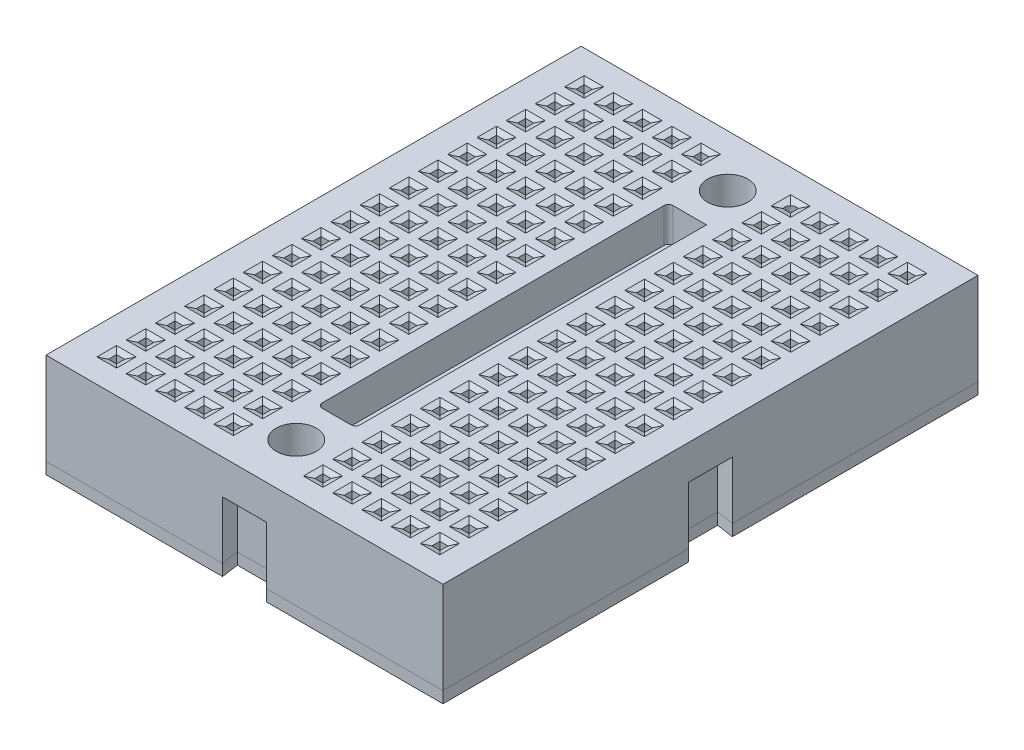
SolidWorks part; units mm, degrees
note: '?' marks a value the reader was unsure of.
ref_plane "Front Plane" through (0, 0, 0) normal (0, 0, 1) x (1, 0, 0)
ref_plane "Top Plane" through (0, 0, 0) normal (0, 1, 0) x (1, 0, 0)
ref_plane "Right Plane" through (0, 0, 0) normal (1, 0, 0) x (0, 0, -1)
sketch "Sketch1" plane through (0, 0, 0) normal (0, 1, 0) x (1, 0, 0)
  line L1 (17.25, -23.25) -> (-17.25, -23.25)
  line L2 (17.25, -23.25) -> (17.25, 23.25)
  line L3 (17.25, 23.25) -> (-17.25, 23.25)
  line L4 (-17.25, -23.25) -> (-17.25, 23.25)
  line L5 (17.25, -23.25) -> (-17.25, 23.25) construction
  line L6 (17.25, 23.25) -> (-17.25, -23.25) construction
  point P0 (0, 0)
  dimension "D1" = 46.5
  dimension "D2" = 34.5
extrude "Boss-Bottom" add sketch "Sketch1" along normal blind 1 from offset 4.5 offset against normal yes
sketch "Sketch2" plane through (0, -3.5, 0) normal (0, 1, 0) x (1, 0, 0)
  line L4 (-17.25, 23.25) -> (-17.25, -23.25)
  line L5 (-17.25, -23.25) -> (17.25, -23.25)
  line L6 (17.25, -23.25) -> (17.25, 23.25)
  line L7 (17.25, 23.25) -> (-17.25, 23.25)
  line L8 (-17.25, 23.25) -> (-17.25, -23.25)
  line L9 (-17.25, -23.25) -> (17.25, -23.25)
  line L10 (17.25, -23.25) -> (17.25, 23.25)
  line L11 (17.25, 23.25) -> (-17.25, 23.25)
  dimension "D2" = 46.5
  dimension "D3" = 34.5
  dimension "D1" = 0
extrude "Boss-Top" add sketch "Sketch2" along normal blind 8 separate body
sketch "Sketch3" plane through (0, 4.5, 0) normal (0, 1, 0) x (1, 0, 0)
  line L0 (0, 15.25) -> (0, 18.75) construction
  line L1 (1.65, -15.25) -> (-1.65, -15.25)
  line L2 (1.65, -15.25) -> (1.65, 15.25)
  line L3 (1.65, 15.25) -> (-1.65, 15.25)
  line L4 (-1.65, -15.25) -> (-1.65, 15.25)
  line L5 (1.65, -15.25) -> (-1.65, 15.25) construction
  line L6 (1.65, 15.25) -> (-1.65, -15.25) construction
  line L7 (0, 0) -> (17.25, 0) construction
  line L8 (17.25, -23.25) -> (17.25, 23.25) construction
  circle A0 centre (0, 18.75) radius 1.75
  circle A1 centre (0, -18.75) radius 1.75
  point P0 (0, 0)
  dimension "D4" = 3.5
  dimension "D1" = 30.5
  dimension "D2" = 3.3
  dimension "D3" = 3.5
extrude "Cut-Middle" cut sketch "Sketch3" against normal blind 3
sketch "Sketch5" plane through (0, 1.5, 0) normal (0, 1, 0) x (1, 0, 0)
  line L0 (0, 0) -> (17.25, 0) construction
  line L1 (17.25, -23.25) -> (17.25, 23.25) construction
  circle A0 centre (0, 18.75) radius 1
  circle A1 centre (0, -18.75) radius 1
  dimension "D1" = 2
extrude "Cut-M2 screw" cut sketch "Sketch5" against normal blind 5
sketch "Sketch6" plane through (0, 4.5, 0) normal (0, 1, 0) x (1, 0, 0)
  line L0 (0, 0) -> (0, 18.75) construction
  line L1 (0, 18.75) -> (16.9, 18.75) construction
  line L2 (16.9, 18.75) -> (16.9, -23.25) construction
  line L3 (-17.25, -23.25) -> (17.25, -23.25) construction
  line L4 (16.9, 18.75) -> (16.9, 23.25) construction
  line L5 (17.25, 23.25) -> (-17.25, 23.25) construction
  line L6 (0, 18.75) -> (0, 23.25) construction
  line L7 (0, 23.25) -> (16.9, 23.25) construction
  line L8 (8.45, 23.25) -> (8.45, 23.05) construction
  line L9 (8.45, 23.05) -> (16.9, 23.05) construction
  line L10 (8.45, 23.05) -> (0, 23.05) construction
  line L11 (11.86, 19.97) -> (11.86, 20.67)
  line L12 (14.4, 19.97) -> (13.7, 19.97)
  line L13 (14.4, 19.97) -> (14.4, 20.67)
  line L14 (14.4, 20.67) -> (13.7, 20.67)
  line L15 (13.7, 19.97) -> (13.7, 20.67)
  line L16 (14.4, 19.97) -> (13.7, 20.67) construction
  line L17 (14.4, 20.67) -> (13.7, 19.97) construction
  line L18 (11.86, 19.97) -> (11.16, 19.97)
  line L19 (11.16, 19.97) -> (11.16, 20.67)
  line L20 (11.86, 20.67) -> (11.16, 20.67)
  line L21 (9.32, 19.97) -> (9.32, 20.67)
  line L22 (9.32, 19.97) -> (8.62, 19.97)
  line L23 (8.62, 19.97) -> (8.62, 20.67)
  line L24 (9.32, 20.67) -> (8.62, 20.67)
  line L25 (6.78, 19.97) -> (6.78, 20.67)
  line L26 (6.78, 19.97) -> (6.08, 19.97)
  line L27 (6.08, 19.97) -> (6.08, 20.67)
  line L28 (6.78, 20.67) -> (6.08, 20.67)
  line L29 (4.24, 19.97) -> (4.24, 20.67)
  line L30 (4.24, 19.97) -> (3.54, 19.97)
  line L31 (3.54, 19.97) -> (3.54, 20.67)
  line L32 (4.24, 20.67) -> (3.54, 20.67)
  line L33 (3.89, 20.67) -> (3.89, 20.32) construction
  line L34 (3.89, 20.32) -> (4.24, 20.32) construction
  point P14 (14.05, 20.32)
  point P39 (6.43, 20.32)
  point P41 (3.89, 20.32)
  point P42 (8.97, 20.32)
  point P43 (11.51, 20.32)
  point P44 (14.05, 20.32)
  dimension "D1" = 16.9
  dimension "D2" = 0.2
  dimension "D3" = 0.7
  dimension "D4" = 2.85
  dimension "D5" = 2.73
  dimension "D6" = 5
extrude "Cut-Extrude3" cut sketch "Sketch6" against normal blind 8
sketch "Sketch7" plane through (0, 4.5, 0) normal (0, 1, 0) x (1, 0, 0)
  line L0 (12.36, 19.47) -> (10.66, 19.47)
  line L1 (14.9, 19.47) -> (13.2, 19.47)
  line L2 (14.9, 19.47) -> (14.9, 21.17)
  line L3 (14.9, 21.17) -> (13.2, 21.17)
  line L4 (13.2, 19.47) -> (13.2, 21.17)
  line L5 (14.9, 19.47) -> (13.2, 21.17) construction
  line L6 (14.9, 21.17) -> (13.2, 19.47) construction
  line L7 (12.36, 19.47) -> (12.36, 21.17)
  line L8 (12.36, 21.17) -> (10.66, 21.17)
  line L9 (10.66, 19.47) -> (10.66, 21.17)
  line L10 (12.36, 19.47) -> (10.66, 21.17) construction
  line L11 (12.36, 21.17) -> (10.66, 19.47) construction
  line L12 (9.82, 19.47) -> (8.12, 19.47)
  line L13 (9.82, 19.47) -> (9.82, 21.17)
  line L14 (9.82, 21.17) -> (8.12, 21.17)
  line L15 (8.12, 19.47) -> (8.12, 21.17)
  line L16 (9.82, 19.47) -> (8.12, 21.17) construction
  line L17 (9.82, 21.17) -> (8.12, 19.47) construction
  line L18 (7.28, 19.47) -> (5.58, 19.47)
  line L19 (7.28, 19.47) -> (7.28, 21.17)
  line L20 (7.28, 21.17) -> (5.58, 21.17)
  line L21 (5.58, 19.47) -> (5.58, 21.17)
  line L22 (7.28, 19.47) -> (5.58, 21.17) construction
  line L23 (7.28, 21.17) -> (5.58, 19.47) construction
  line L24 (4.74, 19.47) -> (3.04, 19.47)
  line L25 (4.74, 19.47) -> (4.74, 21.17)
  line L26 (4.74, 21.17) -> (3.04, 21.17)
  line L27 (3.04, 19.47) -> (3.04, 21.17)
  line L28 (4.74, 19.47) -> (3.04, 21.17) construction
  line L29 (4.74, 21.17) -> (3.04, 19.47) construction
  point P0 (14.05, 20.32)
  point P6 (11.51, 20.32)
  point P11 (8.97, 20.32)
  point P16 (6.43, 20.32)
  point P21 (3.89, 20.32)
  dimension "D1" = 1.7
  dimension "D2" = 5
extrude "Cut-Extrude4" cut sketch "Sketch7" against normal blind 2.54 draft 70
pattern_linear "LPattern3" count 17 spacing 2.54 along (0, 0, 1) of "Cut-Extrude3", "Cut-Extrude4"
mirror "Mirror1" about plane through (0, 0, 0) normal (1, 0, 0) of "LPattern3", "Cut-Extrude3", "Cut-Extrude4"
fillet "Fillet1" radius 0.4 4 edges at (1.65, 3, 15.25) (-1.65, 3, 15.25) (3.54, 0.409, -20.67) (-1.65, 3, -15.25)
sketch "Sketch8" plane through (0, 4.5, 0) normal (0, 1, 0) x (1, 0, 0)
  line L0 (0, 23.25) -> (0, 24.75) construction
  line L1 (1.8928, 24.75) -> (-1.8928, 24.75)
  line L2 (-2.0905, 24.5203) -> (-1.9, 23.25)
  line L3 (-1.9, 23.25) -> (1.9, 23.25)
  line L4 (1.9, 23.25) -> (2.0905, 24.5203)
  line L5 (0, 18.75) -> (0, 23.25) construction
  line L6 (17.25, 23.25) -> (-17.25, 23.25) construction
  line L7 (-17.25, 0) -> (-18.75, 0) construction
  line L8 (-18.75, 1.8928) -> (-18.75, -1.8928)
  line L9 (-18.5203, -2.0905) -> (-17.25, -1.9)
  line L10 (-17.25, -1.9) -> (-17.25, 1.9)
  line L11 (-17.25, 1.9) -> (-18.5203, 2.0905)
  line L12 (0, 0) -> (-17.25, 0) construction
  line L13 (-17.25, 23.25) -> (-17.25, -23.25) construction
  arc A0 (2.0905, 24.5203) -> (1.8928, 24.75) centre (1.8928, 24.55) ccw
  arc A1 (-1.8928, 24.75) -> (-2.0905, 24.5203) centre (-1.8928, 24.55) ccw
  arc A2 (-18.5203, 2.0905) -> (-18.75, 1.8928) centre (-18.55, 1.8928) ccw
  arc A3 (-18.75, -1.8928) -> (-18.5203, -2.0905) centre (-18.55, -1.8928) ccw
extrude "Boss-Connector" add sketch "Sketch8" against normal blind 5 from offset 3 separate body offset against normal yes
sketch "Sketch9" plane through (0, 4.5, 0) normal (0, 1, 0) x (1, 0, 0)
  line L0 (17.25, 0) -> (15.75, 0) construction
  line L1 (15.75, 1.8928) -> (15.75, -1.8928)
  line L2 (15.75, -2.125) -> (17.25, -1.9)
  line L3 (17.25, -1.9) -> (17.25, 1.9)
  line L4 (17.25, 1.9) -> (15.75, 2.125)
  line L5 (0, 0) -> (17.25, 0) construction
  line L6 (17.25, -23.25) -> (17.25, 23.25) construction
  line L7 (0, -23.25) -> (0, -21.75) construction
  line L8 (1.8928, -21.75) -> (-1.8928, -21.75)
  line L9 (-2.125, -21.75) -> (-1.9, -23.25)
  line L10 (-1.9, -23.25) -> (1.9, -23.25)
  line L11 (1.9, -23.25) -> (2.125, -21.75)
  line L12 (0, 0) -> (0, -23.25) construction
  line L13 (-17.25, -23.25) -> (17.25, -23.25) construction
  line L14 (1.8928, -21.75) -> (2.125, -21.75)
  line L15 (-1.8928, -21.75) -> (-2.125, -21.75)
  line L16 (15.75, 1.8928) -> (15.75, 2.125)
  line L17 (15.75, -1.8928) -> (15.75, -2.125)
  arc A0 (15.9797, 2.0905) -> (15.75, 1.8928) centre (15.95, 1.8928) ccw construction
  arc A1 (15.75, -1.8928) -> (15.9797, -2.0905) centre (15.95, -1.8928) ccw construction
  arc A2 (2.0905, -21.9797) -> (1.8928, -21.75) centre (1.8928, -21.95) ccw construction
  arc A3 (-1.8928, -21.75) -> (-2.0905, -21.9797) centre (-1.8928, -21.95) ccw construction
  dimension "D2" = 3.7855
  dimension "D3" = 3.8
  dimension "D5" = 23.25
extrude "Cut-Connector" cut sketch "Sketch9" against normal blind 6 from offset 3 offset against normal yes
ref_plane "Plane1" through (0, 2.5, 0) normal (0, 1, 0) x (1, 0, 0)
sketch "Sketch10" plane through (0, 2.5, 0) normal (0, 1, 0) x (1, 0, 0)
  line L0 (14.4, 20.67) -> (14.9, 21.17) construction
  line L2 (14.4, 19.97) -> (14.9, 19.47) construction
  line L3 (11.16, 19.97) -> (10.66, 19.47) construction
  line L4 (11.16, 20.67) -> (10.66, 21.17) construction
  line L5 (8.62, 20.67) -> (8.12, 21.17) construction
  line L6 (8.62, 19.97) -> (8.12, 19.47) construction
  line L7 (6.78, 20.67) -> (7.28, 21.17) construction
  line L8 (6.78, 19.97) -> (7.28, 19.47) construction
  line L9 (4.24, 19.97) -> (4.74, 19.47) construction
  point P0 (14.05, 20.32)
  point P1 (11.51, 20.32)
  point P2 (8.97, 20.32)
  point P3 (6.43, 20.32)
  point P4 (3.8848, 20.3252)
  point P6 (14.0799, 17.7806)
  point P30 (11.5399, 17.7806)
  point P31 (8.9999, 17.7806)
  point P32 (6.4599, 17.7806)
  point P33 (3.9147, 17.7858)
  point P34 (14.1016, 15.2623)
  point P35 (11.5616, 15.2623)
  point P36 (9.0216, 15.2623)
  point P37 (6.4816, 15.2623)
  point P38 (3.9364, 15.2676)
  point P39 (14.0487, 12.7209)
  point P40 (11.5087, 12.7209)
  point P41 (8.9687, 12.7209)
  point P42 (6.4287, 12.7209)
  point P43 (3.8835, 12.7262)
  point P44 (14.0487, 10.1749)
  point P45 (11.5087, 10.1749)
  point P46 (8.9687, 10.1749)
  point P47 (6.4287, 10.1749)
  point P48 (3.8835, 10.1801)
  point P49 (14.0548, 7.6501)
  point P50 (11.5148, 7.6501)
  point P51 (8.9748, 7.6501)
  point P52 (6.4348, 7.6501)
  point P53 (3.8896, 7.6553)
  point P54 (14.1089, 5.0642)
  point P55 (11.5689, 5.0642)
  point P56 (9.0289, 5.0642)
  point P57 (6.4889, 5.0642)
  point P58 (3.9437, 5.0694)
  point P59 (14.031, 2.5387)
  point P60 (11.491, 2.5387)
  point P61 (8.951, 2.5387)
  point P62 (6.411, 2.5387)
  point P63 (3.8658, 2.5439)
  point P64 (14.0455, -0.0484)
  point P65 (11.5055, -0.0484)
  point P66 (8.9655, -0.0484)
  point P67 (6.4255, -0.0484)
  point P68 (3.8803, -0.0432)
  point P69 (14.0174, -2.484)
  point P70 (11.4774, -2.484)
  point P71 (8.9374, -2.484)
  point P72 (6.3974, -2.484)
  point P73 (3.8521, -2.4788)
  point P74 (13.9866, -5.1019)
  point P75 (11.4466, -5.1019)
  point P76 (8.9066, -5.1019)
  point P77 (6.3666, -5.1019)
  point P78 (3.8213, -5.0967)
  point P79 (13.9866, -7.5966)
  point P80 (11.4466, -7.5966)
  point P81 (8.9066, -7.5966)
  point P82 (6.3666, -7.5966)
  point P83 (3.8213, -7.5914)
  point P84 (14.0174, -10.1529)
  point P85 (11.4774, -10.1529)
  point P86 (8.9374, -10.1529)
  point P87 (6.3974, -10.1529)
  point P88 (3.8521, -10.1476)
  point P89 (14.0719, -12.7703)
  point P90 (11.5319, -12.7703)
  point P91 (8.9919, -12.7703)
  point P92 (6.4519, -12.7703)
  point P93 (3.9067, -12.7651)
  point P99 (8.9893, -0.0026)
  point P100 (6.4493, -0.0026)
  point P101 (3.9093, -0.0026)
  point P103 (-3.9057, -7.6019)
  point P104 (14.0201, -17.8449)
  point P105 (11.4801, -17.8449)
  point P106 (8.9401, -17.8449)
  point P107 (6.4001, -17.8449)
  point P108 (3.8549, -17.8397)
  point P110 (14.0693, -15.2705)
  point P111 (11.5293, -15.2705)
  point P112 (8.9893, -15.2705)
  point P113 (6.4493, -15.2705)
  point P114 (3.9041, -15.2653)
  point P115 (14.0249, -20.3204)
  point P116 (11.4849, -20.3204)
  point P117 (8.9449, -20.3204)
  point P118 (6.4049, -20.3204)
  point P119 (3.8597, -20.3152)
  point P120 (-3.9022, -20.3215)
  point P121 (-6.4422, -20.3215)
  point P122 (-8.9822, -20.3215)
  point P123 (-11.5222, -20.3215)
  point P124 (-14.0674, -20.3163)
  point P130 (-3.9591, -17.7916)
  point P131 (-6.4991, -17.7916)
  point P132 (-9.0391, -17.7916)
  point P133 (-11.5791, -17.7916)
  point P134 (-14.1243, -17.7864)
  point P135 (-3.9306, -15.2901)
  point P136 (-6.4706, -15.2901)
  point P137 (-9.0106, -15.2901)
  point P138 (-11.5506, -15.2901)
  point P139 (-14.0959, -15.2849)
  point P140 (-3.9591, -12.7886)
  point P141 (-6.4991, -12.7886)
  point P142 (-9.0391, -12.7886)
  point P143 (-11.5791, -12.7886)
  point P144 (-14.1243, -12.7834)
  point P145 (-3.9306, -10.2303)
  point P146 (-6.4706, -10.2303)
  point P147 (-9.0106, -10.2303)
  point P148 (-11.5506, -10.2303)
  point P149 (-14.0959, -10.2251)
  point P154 (-6.4457, -7.6019)
  point P155 (-8.9857, -7.6019)
  point P156 (-11.5257, -7.6019)
  point P157 (-14.0709, -7.5967)
  point P158 (-3.9291, -5.0801)
  point P159 (-6.4691, -5.0801)
  point P160 (-9.0091, -5.0801)
  point P161 (-11.5491, -5.0801)
  point P162 (-14.0943, -5.0749)
  point P163 (-3.8809, -2.5371)
  point P164 (-6.4209, -2.5371)
  point P165 (-8.9609, -2.5371)
  point P166 (-11.5009, -2.5371)
  point P167 (-14.0462, -2.5319)
  point P168 (-3.8994, -0.0477)
  point P169 (-6.4394, -0.0477)
  point P170 (-8.9794, -0.0477)
  point P171 (-11.5194, -0.0477)
  point P172 (-14.0646, -0.0425)
  point P173 (-3.8809, 2.497)
  point P174 (-6.4209, 2.497)
  point P175 (-8.9609, 2.497)
  point P176 (-11.5009, 2.497)
  point P177 (-14.0462, 2.5022)
  point P178 (-3.8749, 5.0444)
  point P179 (-6.4149, 5.0444)
  point P180 (-8.9549, 5.0444)
  point P181 (-11.4949, 5.0444)
  point P182 (-14.0401, 5.0496)
  point P183 (-3.9063, 7.6157)
  point P184 (-6.4463, 7.6157)
  point P185 (-8.9863, 7.6157)
  point P186 (-11.5263, 7.6157)
  point P187 (-14.0715, 7.6209)
  point P188 (-3.935, 10.1531)
  point P189 (-6.475, 10.1531)
  point P190 (-9.015, 10.1531)
  point P191 (-11.555, 10.1531)
  point P192 (-14.1002, 10.1583)
  point P193 (-3.935, 12.5989)
  point P194 (-6.475, 12.5989)
  point P195 (-9.015, 12.5989)
  point P196 (-11.555, 12.5989)
  point P197 (-14.1002, 12.6042)
  point P198 (-3.8723, 15.1703)
  point P199 (-6.4123, 15.1703)
  point P200 (-8.9523, 15.1703)
  point P201 (-11.4923, 15.1703)
  point P202 (-14.0375, 15.1755)
  point P203 (-3.935, 17.7102)
  point P204 (-6.475, 17.7102)
  point P205 (-9.015, 17.7102)
  point P206 (-11.555, 17.7102)
  point P207 (-14.1002, 17.7154)
  point P208 (-3.8914, 20.2984)
  point P209 (-6.4314, 20.2984)
  point P210 (-8.9714, 20.2984)
  point P211 (-11.5114, 20.2984)
  point P212 (-14.0566, 20.3036)
fillet "Fillet2" [suppressed] radius 0.4
fillet "Fillet3" [suppressed] radius 0.4
other "CPoint1" parameters "Diameter"=2, "StubLength"=2
ref_axis "Axis1" through (14.05, 12.5, -20.32) along (0, -1, 0)?
other "CPoint2" parameters "Diameter"=2, "StubLength"=2
ref_axis "Axis2" through (11.51, 12.5, -20.32) along (0, -1, 0)?
other "CPoint3" parameters "Diameter"=2, "StubLength"=2
ref_axis "Axis3" through (8.97, 12.5, -20.32) along (0, -1, 0)?
other "CPoint4" parameters "Diameter"=2, "StubLength"=2
ref_axis "Axis4" through (6.43, 12.5, -20.32) along (0, -1, 0)?
other "CPoint5" parameters "Diameter"=2, "StubLength"=2
ref_axis "Axis5" through (3.8848, 12.5, -20.3252) along (0, -1, 0)?
other "CPoint6" parameters "Diameter"=2, "StubLength"=2
ref_axis "Axis6" through (14.0799, 12.5, -17.7806) along (0, -1, 0)?
other "CPoint7" parameters "Diameter"=2, "StubLength"=2
ref_axis "Axis7" through (11.5399, 12.5, -17.7806) along (0, -1, 0)?
other "CPoint8" parameters "Diameter"=2, "StubLength"=2
ref_axis "Axis8" through (8.9999, 12.5, -17.7806) along (0, -1, 0)?
other "CPoint9" parameters "Diameter"=2, "StubLength"=2
ref_axis "Axis9" through (6.4599, 12.5, -17.7806) along (0, -1, 0)?
other "CPoint10" parameters "Diameter"=2, "StubLength"=2
ref_axis "Axis10" through (3.9147, 12.5, -17.7858) along (0, -1, 0)?
other "CPoint11" parameters "Diameter"=2, "StubLength"=2
ref_axis "Axis11" through (14.1016, 12.5, -15.2623) along (0, -1, 0)?
other "CPoint12" parameters "Diameter"=2, "StubLength"=2
ref_axis "Axis12" through (11.5616, 12.5, -15.2623) along (0, -1, 0)?
other "CPoint13" parameters "Diameter"=2, "StubLength"=2
ref_axis "Axis13" through (9.0216, 12.5, -15.2623) along (0, -1, 0)?
other "CPoint14" parameters "Diameter"=2, "StubLength"=2
ref_axis "Axis14" through (6.4816, 12.5, -15.2623) along (0, -1, 0)?
other "CPoint15" parameters "Diameter"=2, "StubLength"=2
ref_axis "Axis15" through (3.9364, 12.5, -15.2676) along (0, -1, 0)?
other "CPoint16" parameters "Diameter"=2, "StubLength"=2
ref_axis "Axis16" through (14.0487, 12.5, -12.7209) along (0, -1, 0)?
other "CPoint17" parameters "Diameter"=2, "StubLength"=2
ref_axis "Axis17" through (11.5087, 12.5, -12.7209) along (0, -1, 0)?
other "CPoint18" parameters "Diameter"=2, "StubLength"=2
ref_axis "Axis18" through (8.9687, 12.5, -12.7209) along (0, -1, 0)?
other "CPoint19" parameters "Diameter"=2, "StubLength"=2
ref_axis "Axis19" through (6.4287, 12.5, -12.7209) along (0, -1, 0)?
other "CPoint20" parameters "Diameter"=2, "StubLength"=2
ref_axis "Axis20" through (3.8835, 12.5, -12.7262) along (0, -1, 0)?
other "CPoint21" parameters "Diameter"=2, "StubLength"=2
ref_axis "Axis21" through (14.0487, 12.5, -10.1749) along (0, -1, 0)?
other "CPoint22" parameters "Diameter"=2, "StubLength"=2
ref_axis "Axis22" through (11.5087, 12.5, -10.1749) along (0, -1, 0)?
other "CPoint23" parameters "Diameter"=2, "StubLength"=2
ref_axis "Axis23" through (8.9687, 12.5, -10.1749) along (0, -1, 0)?
other "CPoint24" parameters "Diameter"=2, "StubLength"=2
ref_axis "Axis24" through (6.4287, 12.5, -10.1749) along (0, -1, 0)?
other "CPoint25" parameters "Diameter"=2, "StubLength"=2
ref_axis "Axis25" through (3.8835, 12.5, -10.1801) along (0, -1, 0)?
other "CPoint26" parameters "Diameter"=2, "StubLength"=2
ref_axis "Axis26" through (14.0548, 12.5, -7.6501) along (0, -1, 0)?
other "CPoint27" parameters "Diameter"=2, "StubLength"=2
ref_axis "Axis27" through (11.5148, 12.5, -7.6501) along (0, -1, 0)?
other "CPoint28" parameters "Diameter"=2, "StubLength"=2
ref_axis "Axis28" through (8.9748, 12.5, -7.6501) along (0, -1, 0)?
other "CPoint29" parameters "Diameter"=2, "StubLength"=2
ref_axis "Axis29" through (6.4348, 12.5, -7.6501) along (0, -1, 0)?
other "CPoint30" parameters "Diameter"=2, "StubLength"=2
ref_axis "Axis30" through (3.8896, 12.5, -7.6553) along (0, -1, 0)?
other "CPoint31" parameters "Diameter"=2, "StubLength"=2
ref_axis "Axis31" through (14.1089, 12.5, -5.0642) along (0, -1, 0)?
other "CPoint32" parameters "Diameter"=2, "StubLength"=2
ref_axis "Axis32" through (11.5689, 12.5, -5.0642) along (0, -1, 0)?
other "CPoint33" parameters "Diameter"=2, "StubLength"=2
ref_axis "Axis33" through (9.0289, 12.5, -5.0642) along (0, -1, 0)?
other "CPoint34" parameters "Diameter"=2, "StubLength"=2
ref_axis "Axis34" through (6.4889, 12.5, -5.0642) along (0, -1, 0)?
other "CPoint35" parameters "Diameter"=2, "StubLength"=2
ref_axis "Axis35" through (3.9437, 12.5, -5.0694) along (0, -1, 0)?
other "CPoint36" parameters "Diameter"=2, "StubLength"=2
ref_axis "Axis36" through (14.031, 12.5, -2.5387) along (0, -1, 0)?
other "CPoint37" parameters "Diameter"=2, "StubLength"=2
ref_axis "Axis37" through (11.491, 12.5, -2.5387) along (0, -1, 0)?
other "CPoint38" parameters "Diameter"=2, "StubLength"=2
ref_axis "Axis38" through (8.951, 12.5, -2.5387) along (0, -1, 0)?
other "CPoint39" parameters "Diameter"=2, "StubLength"=2
ref_axis "Axis39" through (6.411, 12.5, -2.5387) along (0, -1, 0)?
other "CPoint40" parameters "Diameter"=2, "StubLength"=2
ref_axis "Axis40" through (3.8658, 12.5, -2.5439) along (0, -1, 0)?
other "CPoint41" parameters "Diameter"=2, "StubLength"=2
ref_axis "Axis41" through (14.0455, 12.5, 0.0484) along (0, -1, 0)?
other "CPoint42" parameters "Diameter"=2, "StubLength"=2
ref_axis "Axis42" through (11.5055, 12.5, 0.0484) along (0, -1, 0)?
other "CPoint43" parameters "Diameter"=2, "StubLength"=2
ref_axis "Axis43" through (8.9655, 12.5, 0.0484) along (0, -1, 0)?
other "CPoint44" parameters "Diameter"=2, "StubLength"=2
ref_axis "Axis44" through (6.4255, 12.5, 0.0484) along (0, -1, 0)?
other "CPoint45" parameters "Diameter"=2, "StubLength"=2
ref_axis "Axis45" through (3.8803, 12.5, 0.0432) along (0, -1, 0)?
other "CPoint46" parameters "Diameter"=2, "StubLength"=2
ref_axis "Axis46" through (14.0174, 12.5, 2.484) along (0, -1, 0)?
other "CPoint47" parameters "Diameter"=2, "StubLength"=2
ref_axis "Axis47" through (11.4774, 12.5, 2.484) along (0, -1, 0)?
other "CPoint48" parameters "Diameter"=2, "StubLength"=2
ref_axis "Axis48" through (8.9374, 12.5, 2.484) along (0, -1, 0)?
other "CPoint49" parameters "Diameter"=2, "StubLength"=2
ref_axis "Axis49" through (6.3974, 12.5, 2.484) along (0, -1, 0)?
other "CPoint50" parameters "Diameter"=2, "StubLength"=2
ref_axis "Axis50" through (3.8521, 12.5, 2.4788) along (0, -1, 0)?
other "CPoint51" parameters "Diameter"=2, "StubLength"=2
ref_axis "Axis51" through (13.9866, 12.5, 5.1019) along (0, -1, 0)?
other "CPoint52" parameters "Diameter"=2, "StubLength"=2
ref_axis "Axis52" through (11.4466, 12.5, 5.1019) along (0, -1, 0)?
other "CPoint53" parameters "Diameter"=2, "StubLength"=2
ref_axis "Axis53" through (8.9066, 12.5, 5.1019) along (0, -1, 0)?
other "CPoint54" parameters "Diameter"=2, "StubLength"=2
ref_axis "Axis54" through (6.3666, 12.5, 5.1019) along (0, -1, 0)?
other "CPoint55" parameters "Diameter"=2, "StubLength"=2
ref_axis "Axis55" through (3.8213, 12.5, 5.0967) along (0, -1, 0)?
other "CPoint56" parameters "Diameter"=2, "StubLength"=2
ref_axis "Axis56" through (13.9866, 12.5, 7.5966) along (0, -1, 0)?
other "CPoint57" parameters "Diameter"=2, "StubLength"=2
ref_axis "Axis57" through (11.4466, 12.5, 7.5966) along (0, -1, 0)?
other "CPoint58" parameters "Diameter"=2, "StubLength"=2
ref_axis "Axis58" through (8.9066, 12.5, 7.5966) along (0, -1, 0)?
other "CPoint59" parameters "Diameter"=2, "StubLength"=2
ref_axis "Axis59" through (6.3666, 12.5, 7.5966) along (0, -1, 0)?
other "CPoint60" parameters "Diameter"=2, "StubLength"=2
ref_axis "Axis60" through (3.8213, 12.5, 7.5914) along (0, -1, 0)?
other "CPoint61" parameters "Diameter"=2, "StubLength"=2
ref_axis "Axis61" through (14.0174, 12.5, 10.1529) along (0, -1, 0)?
other "CPoint62" parameters "Diameter"=2, "StubLength"=2
ref_axis "Axis62" through (11.4774, 12.5, 10.1529) along (0, -1, 0)?
other "CPoint63" parameters "Diameter"=2, "StubLength"=2
ref_axis "Axis63" through (8.9374, 12.5, 10.1529) along (0, -1, 0)?
other "CPoint64" parameters "Diameter"=2, "StubLength"=2
ref_axis "Axis64" through (6.3974, 12.5, 10.1529) along (0, -1, 0)?
other "CPoint65" parameters "Diameter"=2, "StubLength"=2
ref_axis "Axis65" through (3.8521, 12.5, 10.1476) along (0, -1, 0)?
other "CPoint66" parameters "Diameter"=2, "StubLength"=2
ref_axis "Axis66" through (14.0719, 12.5, 12.7703) along (0, -1, 0)?
other "CPoint67" parameters "Diameter"=2, "StubLength"=2
ref_axis "Axis67" through (11.5319, 12.5, 12.7703) along (0, -1, 0)?
other "CPoint68" parameters "Diameter"=2, "StubLength"=2
ref_axis "Axis68" through (8.9919, 12.5, 12.7703) along (0, -1, 0)?
other "CPoint69" parameters "Diameter"=2, "StubLength"=2
ref_axis "Axis69" through (6.4519, 12.5, 12.7703) along (0, -1, 0)?
other "CPoint70" parameters "Diameter"=2, "StubLength"=2
ref_axis "Axis70" through (3.9067, 12.5, 12.7651) along (0, -1, 0)?
other "CPoint71" parameters "Diameter"=2, "StubLength"=2
ref_axis "Axis71" through (8.9893, 12.5, 0.0026) along (0, -1, 0)?
other "CPoint72" parameters "Diameter"=2, "StubLength"=2
ref_axis "Axis72" through (6.4493, 12.5, 0.0026) along (0, -1, 0)?
other "CPoint73" parameters "Diameter"=2, "StubLength"=2
ref_axis "Axis73" through (3.9093, 12.5, 0.0026) along (0, -1, 0)?
other "CPoint74" parameters "Diameter"=2, "StubLength"=2
ref_axis "Axis74" through (-3.9057, 12.5, 7.6019) along (0, -1, 0)?
other "CPoint75" parameters "Diameter"=2, "StubLength"=2
ref_axis "Axis75" through (14.0201, 12.5, 17.8449) along (0, -1, 0)?
other "CPoint76" parameters "Diameter"=2, "StubLength"=2
ref_axis "Axis76" through (11.4801, 12.5, 17.8449) along (0, -1, 0)?
other "CPoint77" parameters "Diameter"=2, "StubLength"=2
ref_axis "Axis77" through (8.9401, 12.5, 17.8449) along (0, -1, 0)?
other "CPoint78" parameters "Diameter"=2, "StubLength"=2
ref_axis "Axis78" through (6.4001, 12.5, 17.8449) along (0, -1, 0)?
other "CPoint79" parameters "Diameter"=2, "StubLength"=2
ref_axis "Axis79" through (3.8549, 12.5, 17.8397) along (0, -1, 0)?
other "CPoint80" parameters "Diameter"=2, "StubLength"=2
ref_axis "Axis80" through (14.0693, 12.5, 15.2705) along (0, -1, 0)?
other "CPoint81" parameters "Diameter"=2, "StubLength"=2
ref_axis "Axis81" through (11.5293, 12.5, 15.2705) along (0, -1, 0)?
other "CPoint82" parameters "Diameter"=2, "StubLength"=2
ref_axis "Axis82" through (8.9893, 12.5, 15.2705) along (0, -1, 0)?
other "CPoint83" parameters "Diameter"=2, "StubLength"=2
ref_axis "Axis83" through (6.4493, 12.5, 15.2705) along (0, -1, 0)?
other "CPoint84" parameters "Diameter"=2, "StubLength"=2
ref_axis "Axis84" through (3.9041, 12.5, 15.2653) along (0, -1, 0)?
other "CPoint85" parameters "Diameter"=2, "StubLength"=2
ref_axis "Axis85" through (14.0249, 12.5, 20.3204) along (0, -1, 0)?
other "CPoint86" parameters "Diameter"=2, "StubLength"=2
ref_axis "Axis86" through (11.4849, 12.5, 20.3204) along (0, -1, 0)?
other "CPoint87" parameters "Diameter"=2, "StubLength"=2
ref_axis "Axis87" through (8.9449, 12.5, 20.3204) along (0, -1, 0)?
other "CPoint88" parameters "Diameter"=2, "StubLength"=2
ref_axis "Axis88" through (6.4049, 12.5, 20.3204) along (0, -1, 0)?
other "CPoint89" parameters "Diameter"=2, "StubLength"=2
ref_axis "Axis89" through (3.8597, 12.5, 20.3152) along (0, -1, 0)?
other "CPoint90" parameters "Diameter"=2, "StubLength"=2
ref_axis "Axis90" through (-3.9022, 12.5, 20.3215) along (0, -1, 0)?
other "CPoint91" parameters "Diameter"=2, "StubLength"=2
ref_axis "Axis91" through (-6.4422, 12.5, 20.3215) along (0, -1, 0)?
other "CPoint92" parameters "Diameter"=2, "StubLength"=2
ref_axis "Axis92" through (-8.9822, 12.5, 20.3215) along (0, -1, 0)?
other "CPoint93" parameters "Diameter"=2, "StubLength"=2
ref_axis "Axis93" through (-11.5222, 12.5, 20.3215) along (0, -1, 0)?
other "CPoint94" parameters "Diameter"=2, "StubLength"=2
ref_axis "Axis94" through (-14.0674, 12.5, 20.3163) along (0, -1, 0)?
other "CPoint95" parameters "Diameter"=2, "StubLength"=2
ref_axis "Axis95" through (-3.9591, 12.5, 17.7916) along (0, -1, 0)?
other "CPoint96" parameters "Diameter"=2, "StubLength"=2
ref_axis "Axis96" through (-6.4991, 12.5, 17.7916) along (0, -1, 0)?
other "CPoint97" parameters "Diameter"=2, "StubLength"=2
ref_axis "Axis97" through (-9.0391, 12.5, 17.7916) along (0, -1, 0)?
other "CPoint98" parameters "Diameter"=2, "StubLength"=2
ref_axis "Axis98" through (-11.5791, 12.5, 17.7916) along (0, -1, 0)?
other "CPoint99" parameters "Diameter"=2, "StubLength"=2
ref_axis "Axis99" through (-14.1243, 12.5, 17.7864) along (0, -1, 0)?
other "CPoint100" parameters "Diameter"=2, "StubLength"=2
ref_axis "Axis100" through (-3.9306, 12.5, 15.2901) along (0, -1, 0)?
other "CPoint101" parameters "Diameter"=2, "StubLength"=2
ref_axis "Axis101" through (-6.4706, 12.5, 15.2901) along (0, -1, 0)?
other "CPoint102" parameters "Diameter"=2, "StubLength"=2
ref_axis "Axis102" through (-9.0106, 12.5, 15.2901) along (0, -1, 0)?
other "CPoint103" parameters "Diameter"=2, "StubLength"=2
ref_axis "Axis103" through (-11.5506, 12.5, 15.2901) along (0, -1, 0)?
other "CPoint104" parameters "Diameter"=2, "StubLength"=2
ref_axis "Axis104" through (-14.0959, 12.5, 15.2849) along (0, -1, 0)?
other "CPoint105" parameters "Diameter"=2, "StubLength"=2
ref_axis "Axis105" through (-3.9591, 12.5, 12.7886) along (0, -1, 0)?
other "CPoint106" parameters "Diameter"=2, "StubLength"=2
ref_axis "Axis106" through (-6.4991, 12.5, 12.7886) along (0, -1, 0)?
other "CPoint107" parameters "Diameter"=2, "StubLength"=2
ref_axis "Axis107" through (-9.0391, 12.5, 12.7886) along (0, -1, 0)?
other "CPoint108" parameters "Diameter"=2, "StubLength"=2
ref_axis "Axis108" through (-11.5791, 12.5, 12.7886) along (0, -1, 0)?
other "CPoint109" parameters "Diameter"=2, "StubLength"=2
ref_axis "Axis109" through (-14.1243, 12.5, 12.7834) along (0, -1, 0)?
other "CPoint110" parameters "Diameter"=2, "StubLength"=2
ref_axis "Axis110" through (-3.9306, 12.5, 10.2303) along (0, -1, 0)?
other "CPoint111" parameters "Diameter"=2, "StubLength"=2
ref_axis "Axis111" through (-6.4706, 12.5, 10.2303) along (0, -1, 0)?
other "CPoint112" parameters "Diameter"=2, "StubLength"=2
ref_axis "Axis112" through (-9.0106, 12.5, 10.2303) along (0, -1, 0)?
other "CPoint113" parameters "Diameter"=2, "StubLength"=2
ref_axis "Axis113" through (-11.5506, 12.5, 10.2303) along (0, -1, 0)?
other "CPoint114" parameters "Diameter"=2, "StubLength"=2
ref_axis "Axis114" through (-14.0959, 12.5, 10.2251) along (0, -1, 0)?
other "CPoint115" parameters "Diameter"=2, "StubLength"=2
ref_axis "Axis115" through (-6.4457, 12.5, 7.6019) along (0, -1, 0)?
other "CPoint116" parameters "Diameter"=2, "StubLength"=2
ref_axis "Axis116" through (-8.9857, 12.5, 7.6019) along (0, -1, 0)?
other "CPoint117" parameters "Diameter"=2, "StubLength"=2
ref_axis "Axis117" through (-11.5257, 12.5, 7.6019) along (0, -1, 0)?
other "CPoint118" parameters "Diameter"=2, "StubLength"=2
ref_axis "Axis118" through (-14.0709, 12.5, 7.5967) along (0, -1, 0)?
other "CPoint119" parameters "Diameter"=2, "StubLength"=2
ref_axis "Axis119" through (-3.9291, 12.5, 5.0801) along (0, -1, 0)?
other "CPoint120" parameters "Diameter"=2, "StubLength"=2
ref_axis "Axis120" through (-6.4691, 12.5, 5.0801) along (0, -1, 0)?
other "CPoint121" parameters "Diameter"=2, "StubLength"=2
ref_axis "Axis121" through (-9.0091, 12.5, 5.0801) along (0, -1, 0)?
other "CPoint122" parameters "Diameter"=2, "StubLength"=2
ref_axis "Axis122" through (-11.5491, 12.5, 5.0801) along (0, -1, 0)?
other "CPoint123" parameters "Diameter"=2, "StubLength"=2
ref_axis "Axis123" through (-14.0943, 12.5, 5.0749) along (0, -1, 0)?
other "CPoint124" parameters "Diameter"=2, "StubLength"=2
ref_axis "Axis124" through (-3.8809, 12.5, 2.5371) along (0, -1, 0)?
other "CPoint125" parameters "Diameter"=2, "StubLength"=2
ref_axis "Axis125" through (-6.4209, 12.5, 2.5371) along (0, -1, 0)?
other "CPoint126" parameters "Diameter"=2, "StubLength"=2
ref_axis "Axis126" through (-8.9609, 12.5, 2.5371) along (0, -1, 0)?
other "CPoint127" parameters "Diameter"=2, "StubLength"=2
ref_axis "Axis127" through (-11.5009, 12.5, 2.5371) along (0, -1, 0)?
other "CPoint128" parameters "Diameter"=2, "StubLength"=2
ref_axis "Axis128" through (-14.0462, 12.5, 2.5319) along (0, -1, 0)?
other "CPoint129" parameters "Diameter"=2, "StubLength"=2
ref_axis "Axis129" through (-3.8994, 12.5, 0.0477) along (0, -1, 0)?
other "CPoint130" parameters "Diameter"=2, "StubLength"=2
ref_axis "Axis130" through (-6.4394, 12.5, 0.0477) along (0, -1, 0)?
other "CPoint131" parameters "Diameter"=2, "StubLength"=2
ref_axis "Axis131" through (-8.9794, 12.5, 0.0477) along (0, -1, 0)?
other "CPoint132" parameters "Diameter"=2, "StubLength"=2
ref_axis "Axis132" through (-11.5194, 12.5, 0.0477) along (0, -1, 0)?
other "CPoint133" parameters "Diameter"=2, "StubLength"=2
ref_axis "Axis133" through (-14.0646, 12.5, 0.0425) along (0, -1, 0)?
other "CPoint134" parameters "Diameter"=2, "StubLength"=2
ref_axis "Axis134" through (-3.8809, 12.5, -2.497) along (0, -1, 0)?
other "CPoint135" parameters "Diameter"=2, "StubLength"=2
ref_axis "Axis135" through (-6.4209, 12.5, -2.497) along (0, -1, 0)?
other "CPoint136" parameters "Diameter"=2, "StubLength"=2
ref_axis "Axis136" through (-8.9609, 12.5, -2.497) along (0, -1, 0)?
other "CPoint137" parameters "Diameter"=2, "StubLength"=2
ref_axis "Axis137" through (-11.5009, 12.5, -2.497) along (0, -1, 0)?
other "CPoint138" parameters "Diameter"=2, "StubLength"=2
ref_axis "Axis138" through (-14.0462, 12.5, -2.5022) along (0, -1, 0)?
other "CPoint139" parameters "Diameter"=2, "StubLength"=2
ref_axis "Axis139" through (-3.8749, 12.5, -5.0444) along (0, -1, 0)?
other "CPoint140" parameters "Diameter"=2, "StubLength"=2
ref_axis "Axis140" through (-6.4149, 12.5, -5.0444) along (0, -1, 0)?
other "CPoint141" parameters "Diameter"=2, "StubLength"=2
ref_axis "Axis141" through (-8.9549, 12.5, -5.0444) along (0, -1, 0)?
other "CPoint142" parameters "Diameter"=2, "StubLength"=2
ref_axis "Axis142" through (-11.4949, 12.5, -5.0444) along (0, -1, 0)?
other "CPoint143" parameters "Diameter"=2, "StubLength"=2
ref_axis "Axis143" through (-14.0401, 12.5, -5.0496) along (0, -1, 0)?
other "CPoint144" parameters "Diameter"=2, "StubLength"=2
ref_axis "Axis144" through (-3.9063, 12.5, -7.6157) along (0, -1, 0)?
other "CPoint145" parameters "Diameter"=2, "StubLength"=2
ref_axis "Axis145" through (-6.4463, 12.5, -7.6157) along (0, -1, 0)?
other "CPoint146" parameters "Diameter"=2, "StubLength"=2
ref_axis "Axis146" through (-8.9863, 12.5, -7.6157) along (0, -1, 0)?
other "CPoint147" parameters "Diameter"=2, "StubLength"=2
ref_axis "Axis147" through (-11.5263, 12.5, -7.6157) along (0, -1, 0)?
other "CPoint148" parameters "Diameter"=2, "StubLength"=2
ref_axis "Axis148" through (-14.0715, 12.5, -7.6209) along (0, -1, 0)?
other "CPoint149" parameters "Diameter"=2, "StubLength"=2
ref_axis "Axis149" through (-3.935, 12.5, -10.1531) along (0, -1, 0)?
other "CPoint150" parameters "Diameter"=2, "StubLength"=2
ref_axis "Axis150" through (-6.475, 12.5, -10.1531) along (0, -1, 0)?
other "CPoint151" parameters "Diameter"=2, "StubLength"=2
ref_axis "Axis151" through (-9.015, 12.5, -10.1531) along (0, -1, 0)?
other "CPoint152" parameters "Diameter"=2, "StubLength"=2
ref_axis "Axis152" through (-11.555, 12.5, -10.1531) along (0, -1, 0)?
other "CPoint153" parameters "Diameter"=2, "StubLength"=2
ref_axis "Axis153" through (-14.1002, 12.5, -10.1583) along (0, -1, 0)?
other "CPoint154" parameters "Diameter"=2, "StubLength"=2
ref_axis "Axis154" through (-3.935, 12.5, -12.5989) along (0, -1, 0)?
other "CPoint155" parameters "Diameter"=2, "StubLength"=2
ref_axis "Axis155" through (-6.475, 12.5, -12.5989) along (0, -1, 0)?
other "CPoint156" parameters "Diameter"=2, "StubLength"=2
ref_axis "Axis156" through (-9.015, 12.5, -12.5989) along (0, -1, 0)?
other "CPoint157" parameters "Diameter"=2, "StubLength"=2
ref_axis "Axis157" through (-11.555, 12.5, -12.5989) along (0, -1, 0)?
other "CPoint158" parameters "Diameter"=2, "StubLength"=2
ref_axis "Axis158" through (-14.1002, 12.5, -12.6042) along (0, -1, 0)?
other "CPoint159" parameters "Diameter"=2, "StubLength"=2
ref_axis "Axis159" through (-3.8723, 12.5, -15.1703) along (0, -1, 0)?
other "CPoint160" parameters "Diameter"=2, "StubLength"=2
ref_axis "Axis160" through (-6.4123, 12.5, -15.1703) along (0, -1, 0)?
other "CPoint161" parameters "Diameter"=2, "StubLength"=2
ref_axis "Axis161" through (-8.9523, 12.5, -15.1703) along (0, -1, 0)?
other "CPoint162" parameters "Diameter"=2, "StubLength"=2
ref_axis "Axis162" through (-11.4923, 12.5, -15.1703) along (0, -1, 0)?
other "CPoint163" parameters "Diameter"=2, "StubLength"=2
ref_axis "Axis163" through (-14.0375, 12.5, -15.1755) along (0, -1, 0)?
other "CPoint164" parameters "Diameter"=2, "StubLength"=2
ref_axis "Axis164" through (-3.935, 12.5, -17.7102) along (0, -1, 0)?
other "CPoint165" parameters "Diameter"=2, "StubLength"=2
ref_axis "Axis165" through (-6.475, 12.5, -17.7102) along (0, -1, 0)?
other "CPoint166" parameters "Diameter"=2, "StubLength"=2
ref_axis "Axis166" through (-9.015, 12.5, -17.7102) along (0, -1, 0)?
other "CPoint167" parameters "Diameter"=2, "StubLength"=2
ref_axis "Axis167" through (-11.555, 12.5, -17.7102) along (0, -1, 0)?
other "CPoint168" parameters "Diameter"=2, "StubLength"=2
ref_axis "Axis168" through (-14.1002, 12.5, -17.7154) along (0, -1, 0)?
other "CPoint169" parameters "Diameter"=2, "StubLength"=2
ref_axis "Axis169" through (-3.8914, 12.5, -20.2984) along (0, -1, 0)?
other "CPoint170" parameters "Diameter"=2, "StubLength"=2
ref_axis "Axis170" through (-6.4314, 12.5, -20.2984) along (0, -1, 0)?
other "CPoint171" parameters "Diameter"=2, "StubLength"=2
ref_axis "Axis171" through (-8.9714, 12.5, -20.2984) along (0, -1, 0)?
other "CPoint172" parameters "Diameter"=2, "StubLength"=2
ref_axis "Axis172" through (-11.5114, 12.5, -20.2984) along (0, -1, 0)?
other "CPoint173" parameters "Diameter"=2, "StubLength"=2
ref_axis "Axis173" through (-14.0566, 12.5, -20.3036) along (0, -1, 0)?
other "CPoint174" parameters "Diameter"=2, "StubLength"=2
ref_axis "Axis174" through (0, 14.5, 18.75) along (0, -1, 0)?
